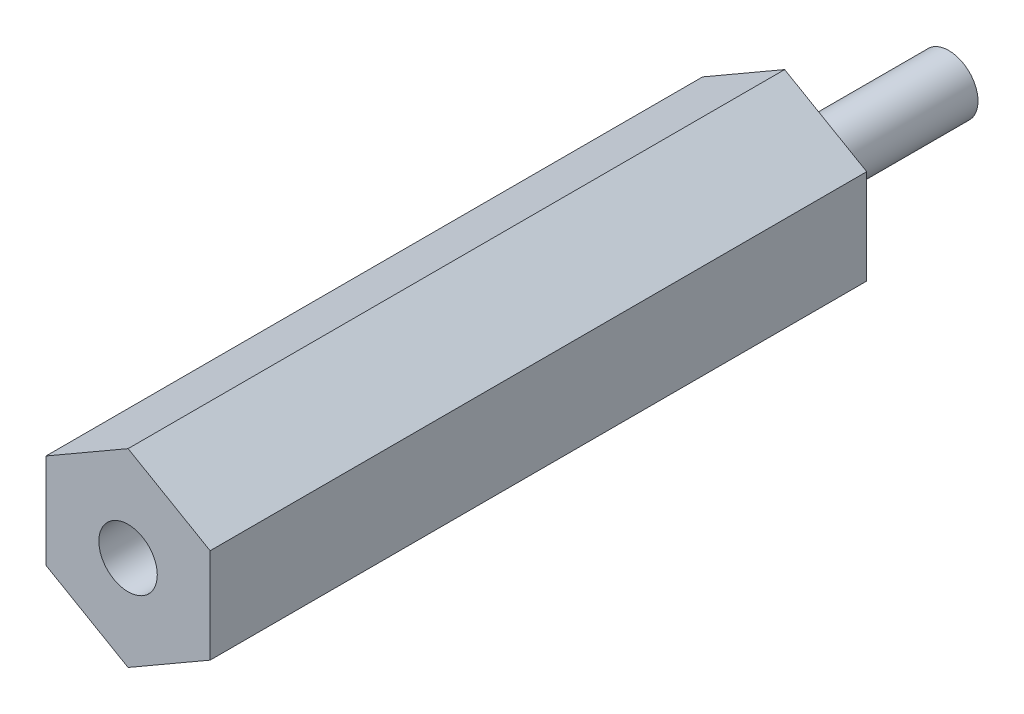
SolidWorks part; units mm, degrees
material "5052-H32"
ref_plane "Front Plane" through (0, 0, 0) normal (0, 0, 1) x (1, 0, 0)
ref_plane "Top Plane" through (0, 0, 0) normal (0, 1, 0) x (1, 0, 0)
ref_plane "Right Plane" through (0, 0, 0) normal (1, 0, 0) x (0, 0, -1)
sketch "Sketch1" plane through (0, 0, 0) normal (0, 0, 1) x (1, 0, 0)
  line L1 (0, 3.6662) -> (-3.175, 1.8331)
  line L2 (-3.175, 1.8331) -> (-3.175, -1.8331)
  line L3 (-3.175, -1.8331) -> (0, -3.6662)
  line L4 (0, -3.6662) -> (3.175, -1.8331)
  line L5 (3.175, -1.8331) -> (3.175, 1.8331)
  line L6 (3.175, 1.8331) -> (0, 3.6662)
  circle A0 centre (0, 0) radius 3.175 construction
  dimension "D1" = 6.35
extrude "Boss-Extrude1" add sketch "Sketch1" along normal blind 25.4
hole_wizard "Tap Drill for #4-40 Tap1" positions "Sketch3" profile "Sketch2" hole size "#4-40" standard "ANSI Inch"
sketch "Sketch3" plane through (0, 0, 25.4) normal (0, 0, 1) x (1, 0, 0)
  point P0 (0, 0)
sketch "Sketch2" plane through (0, 0, 25.4) normal (1, 0, 0) x (0, -1, 0)
  line L0 (0, 0) -> (0, 13.3792)
  line L1 (0, 13.3792) -> (1.1303, 12.7)
  line L2 (1.1303, 12.7) -> (1.1303, 0)
  line L5 (1.1303, 0) -> (0, 0)
  line L10 (0, 13.3792) -> (-1.1303, 12.7) construction
  line L11 (0, -6.35) -> (0, 107.95) construction
  dimension "Hole Dia." = 2.2606
  dimension "Hole Depth" = 12.7
  dimension "Drill Angle" = 118
sketch "Sketch5" plane through (0, 0, 0) normal (0, 0, -1) x (-1, 0, 0)
  circle A0 centre (0, 0) radius 1.1303
  circle A1 centre (0, 0) radius 1.1303 construction
extrude "Boss-Extrude2" add sketch "Sketch5" along normal blind 6.35
